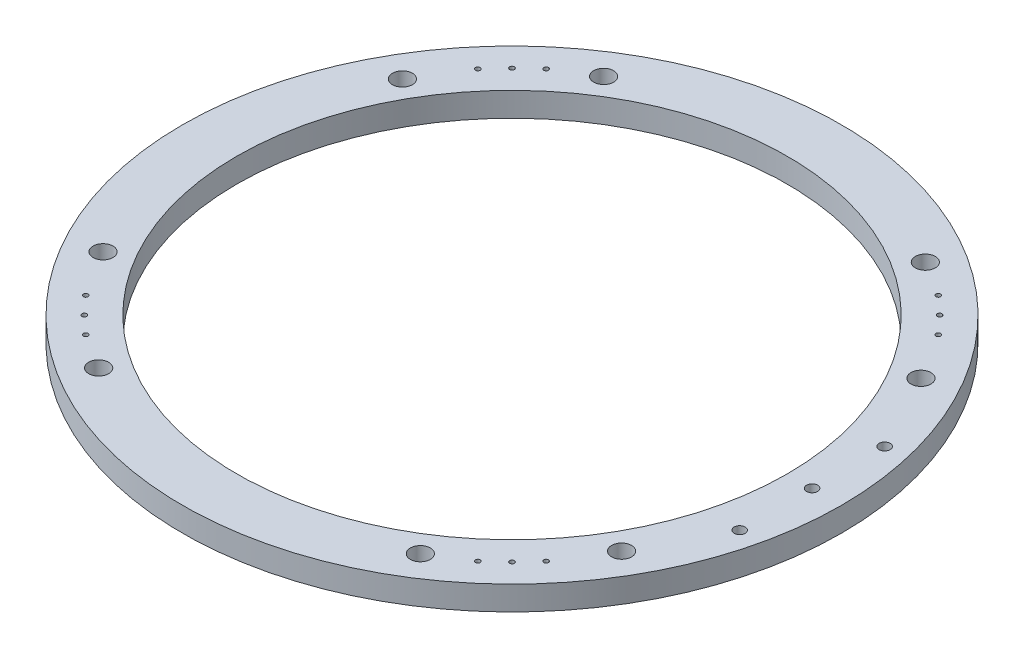
SolidWorks part; units mm, degrees
material "Oak"
ref_plane "Front Plane" through (0, 0, 0) normal (0, 0, 1) x (1, 0, 0)
ref_plane "Top Plane" through (0, 0, 0) normal (0, 1, 0) x (1, 0, 0)
ref_plane "Right Plane" through (0, 0, 0) normal (1, 0, 0) x (0, 0, -1)
sketch "Sketch1" plane through (0, 0, 0) normal (0, 0, 1) x (1, 0, 0)
  line L0 (0, 1125.8152) -> (0, -48874.1848) construction
  line L1 (144.6985, 1004.7732) -> (152.4, 1004.7732)
  line L9 (144.6985, 1017.4732) -> (173.2735, 1017.4732)
  line L10 (144.6985, 1017.4732) -> (144.6985, 1004.7732)
  line L11 (144.6985, 1004.7732) -> (173.2735, 1004.7732)
  line L12 (173.2735, 1017.4732) -> (173.2735, 1004.7732)
revolve "Revolve1" add sketch "Sketch1" angle 360 about L0 region at (158.986, 1011.1232, 0)
hole_wizard "Tap Drill for M3x0.5 Tap1" positions "Sketch9" profile "Sketch10" hole size "M3x0.5" standard "ANSI Metric" end condition through all
sketch "Sketch9" plane through (0, 1004.7732, 0) normal (0, -1, 0) x (-1, 0, 0)
  line L0 (0, 0) -> (112.4201, 112.4201) construction
  line L3 (0, 0) -> (103.0806, 121.0411) construction
  arc A0 (103.0806, 121.0411) -> (121.0411, 103.0806) centre (0, 0) cw
  circle A1 centre (0, 0) radius 158.986 construction
  point P0 (103.0806, 121.0411)
  point P2 (121.0411, 103.0806)
  point P15 (112.4201, 112.4201)
sketch "Sketch10" plane through (-103.0806, 1004.7732, -121.0411) normal (1, 0, 0) x (0, 0, -1)
  line L0 (0, 0) -> (0, 12.7)
  line L1 (0, 12.7) -> (1.25, 12.7)
  line L2 (1.25, 12.7) -> (1.25, 0)
  line L5 (1.25, 0) -> (0, 0)
  line L11 (0, -6.35) -> (0, 107.95) construction
  dimension "Thru Hole Dia." = 2.5
  dimension "Thru Hole Depth" = 12.7
pattern_circular "CirPattern1" count 4 over 360 about axis through (0, 1125.8152, 0) along (0, 1, 0) of "Tap Drill for M3x0.5 Tap1"
ref_plane "Plane1" through (0, 1011.1232, 0) normal (0, 1, 0) x (1, 0, 0)
hole_wizard "M5 Clearance Hole1" positions "Sketch14" profile "Sketch15" hole size "M5" standard "ANSI Metric" end condition through all
sketch "Sketch14" plane through (0, 1017.4732, 0) normal (0, 1, 0) x (1, 0, 0)
  line L0 (157.7975, -38.1) -> (157.7975, 38.1) construction
  point P9 (157.7975, -38.1)
  point P12 (157.7975, 0)
  point P14 (157.7975, 38.1)
sketch "Sketch15" plane through (157.7975, 1017.4732, 38.1) normal (1, 0, 0) x (0, 0, 1)
  line L0 (0, 0) -> (0, 12.7)
  line L1 (0, 12.7) -> (2.9, 12.7)
  line L2 (2.9, 12.7) -> (2.9, 0)
  line L5 (2.9, 0) -> (0, 0)
  line L11 (0, -6.35) -> (0, 107.95) construction
  dimension "Thru Hole Dia." = 5.8
  dimension "Thru Hole Depth" = 12.7
hole_wizard "Z (0.413) Diameter Hole1" positions "Sketch16" profile "Sketch17" hole size "Z" standard "ANSI Inch" end condition through all
sketch "Sketch16" plane through (0, 1017.4732, 0) normal (0, 1, 0) x (1, 0, 0)
  line L0 (-136.3111, -78.6992) -> (136.3111, 78.6992) construction
  line L4 (136.3111, -78.6992) -> (-136.3111, 78.6992) construction
  line L6 (0, 0) -> (0, 157.3985) construction
  line L8 (-84.5701, -132.7485) -> (84.5701, 132.7485) construction
  line L11 (-84.5701, 132.7485) -> (84.5701, -132.7485) construction
  circle A0 centre (0, 0) radius 157.3985 construction
  circle A1 centre (0, 0) radius 144.6985 construction
  point P0 (-136.3111, -78.6992)
  point P2 (136.3111, -78.6992)
  point P4 (136.3111, 78.6992)
  point P6 (-136.3111, 78.6992)
  point P37 (-84.5701, 132.7485)
  point P39 (84.5701, 132.7485)
  point P41 (84.5701, -132.7485)
  point P43 (-84.5701, -132.7485)
  dimension "D2" = 12.7
  dimension "D1" = 120
  dimension "D3" = 65
sketch "Sketch17" plane through (-136.3111, 1017.4732, 78.6992) normal (1, 0, 0) x (0, 0, 1)
  line L0 (0, 0) -> (0, 12.7)
  line L1 (0, 12.7) -> (5.2451, 12.7)
  line L2 (5.2451, 12.7) -> (5.2451, 0)
  line L5 (5.2451, 0) -> (0, 0)
  line L11 (0, -6.35) -> (0, 107.95) construction
  dimension "Thru Hole Dia." = 10.4902
  dimension "Thru Hole Depth" = 12.7
sketch "Sketch18" plane through (0, 1017.4732, 0) normal (0, 1, 0) x (1, 0, 0)
  circle A5 centre (-103.0806, 121.0411) radius 1.5875
  circle A6 centre (-112.4201, 112.4201) radius 1.5875
  circle A7 centre (-121.0411, 103.0806) radius 1.5875
  circle A10 centre (103.0806, 121.0411) radius 1.5875
  circle A11 centre (112.4201, 112.4201) radius 1.5875
  circle A12 centre (121.0411, 103.0806) radius 1.5875
  circle A14 centre (-121.0411, -103.0806) radius 1.5875
  circle A37 centre (-112.4201, -112.4201) radius 1.5875
  circle A38 centre (-103.0806, -121.0411) radius 1.5875
  circle A39 centre (103.0806, -121.0411) radius 1.5875
  circle A40 centre (112.4201, -112.4201) radius 1.5875
  circle A41 centre (121.0411, -103.0806) radius 1.5875
  circle A53 centre (103.0806, 121.0411) radius 1.25
  circle A54 centre (103.0806, 121.0411) radius 1.25
  circle A55 centre (112.4201, 112.4201) radius 1.25
  circle A56 centre (112.4201, 112.4201) radius 1.25
  circle A57 centre (103.0806, -121.0411) radius 1.25
  circle A58 centre (103.0806, -121.0411) radius 1.25
  circle A59 centre (-121.0411, -103.0806) radius 1.25
  circle A60 centre (-121.0411, -103.0806) radius 1.25
  circle A61 centre (-103.0806, -121.0411) radius 1.25
  circle A62 centre (-103.0806, -121.0411) radius 1.25
  circle A63 centre (-112.4201, -112.4201) radius 1.25
  circle A64 centre (-112.4201, -112.4201) radius 1.25
  circle A65 centre (-103.0806, 121.0411) radius 1.25
  circle A66 centre (-103.0806, 121.0411) radius 1.25
  circle A67 centre (-121.0411, 103.0806) radius 1.25
  circle A68 centre (-121.0411, 103.0806) radius 1.25
  circle A69 centre (-112.4201, 112.4201) radius 1.25
  circle A70 centre (-112.4201, 112.4201) radius 1.25
  circle A73 centre (112.4201, -112.4201) radius 1.25
  circle A74 centre (112.4201, -112.4201) radius 1.25
  circle A75 centre (121.0411, -103.0806) radius 1.25
  circle A76 centre (121.0411, -103.0806) radius 1.25
  circle A77 centre (121.0411, 103.0806) radius 1.25
  circle A78 centre (121.0411, 103.0806) radius 1.25
  dimension "D13" = 3.175
  dimension "D14" = 0
  dimension "D15" = 0
  dimension "D16" = 0
  dimension "D17" = 0
  dimension "D18" = 0
  dimension "D19" = 0
  dimension "D20" = 0
  dimension "D21" = 0
  dimension "D22" = 0
  dimension "D24" = 0
  dimension "D25" = 0
  dimension "D26" = 0
extrude "Boss-Extrude1" [suppressed] add sketch "Sketch18" against normal up to surface (12.7 mm away) up to face at (-136.3111, 1004.7732, 83.9443)
